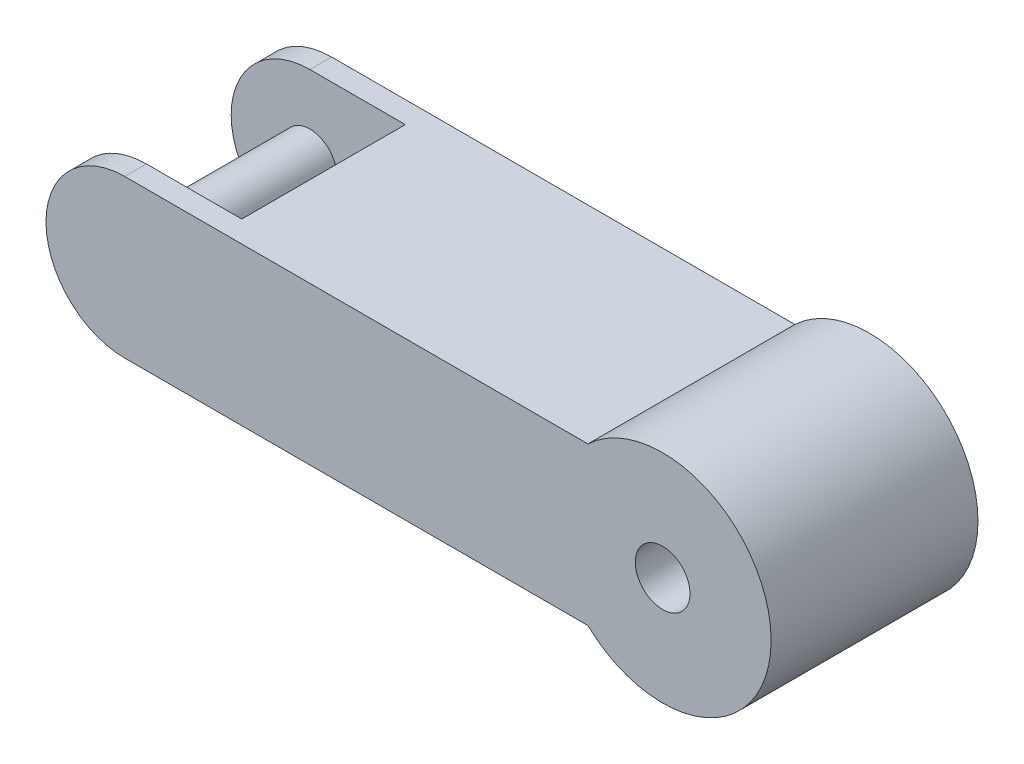
SolidWorks part; units mm, degrees
ref_plane "Front Plane" through (0, 0, 0) normal (0, 0, 1) x (1, 0, 0)
ref_plane "Top Plane" through (0, 0, 0) normal (0, 1, 0) x (1, 0, 0)
ref_plane "Right Plane" through (0, 0, 0) normal (1, 0, 0) x (0, 0, -1)
sketch "Sketch1" plane through (0, 0, 0) normal (0, 0, 1) x (1, 0, 0)
  line L1 (-13.7697, -14.5051) -> (-99.2033, -14.5051)
  line L3 (-13.7697, 14.5051) -> (-99.2033, 14.5051)
  line L5 (-94.0629, 13.5637) -> (-99.2033, 14.5051) construction
  line L6 (-94.0629, -13.5637) -> (-99.2033, -14.5051) construction
  circle A0 centre (0, 0) radius 20
  circle A1 centre (-99.2033, 0) radius 14.5051
  point P3 (-20, 0)
extrude "Boss-Extrude1" add sketch "Sketch1" along normal blind 4 contours A0 | A1 L1 A0 L3 | A1 region at (-52.9937, 0, 0) region at (0, 0, 0) region at (-99.2033, 0, 0)
sketch "Sketch2" plane through (0, 0, 4) normal (0, 0, 1) x (1, 0, 0)
  line L0 (-13.7697, 14.5051) -> (-99.2033, 14.5051) construction
  line L1 (-13.7697, -14.5051) -> (-99.2033, -14.5051) construction
  line L4 (-13.7697, 14.5051) -> (-99.2033, 14.5051)
  line L5 (-99.2033, -14.5051) -> (-13.7697, -14.5051)
  line L6 (-13.7697, 14.5051) -> (-83.4025, 14.5051)
  line L7 (-81.6041, -14.5051) -> (-13.7697, -14.5051)
  arc A0 (-83.4025, 14.5051) -> (-81.6041, -14.5051) centre (-82.5033, 0) cw
  arc A3 (-13.7697, -14.5051) -> (-13.7697, 14.5051) centre (0, 0) ccw
  arc A4 (-99.2033, 14.5051) -> (-99.2033, -14.5051) centre (-99.2033, 0) ccw
  arc A5 (-13.7697, -14.5051) -> (-13.7697, 14.5051) centre (0, 0) ccw
  arc M5 (-13.7697, -14.5051) -> (-13.7697, 14.5051) centre (0, 0) ccw
  line M6 (-13.7697, 14.5051) -> (-99.2033, 14.5051)
  line M8 (-99.2033, -14.5051) -> (-13.7697, -14.5051)
  dimension "D1" = 0
extrude "Boss-Extrude2" add sketch "Sketch2" along normal blind 15.075 contours A0 M6 M8 M5 region at (-24.5614, 0, 4)
mirror "Mirror1" about plane through (0, 0, 19.075) normal (0, 0, 1) of bodies 102
sketch "Sketch3" plane through (0, 0, 0) normal (0, 0, -1) x (-1, 0, 0)
  circle A0 centre (0, 0) radius 5.05
extrude "Cut-Extrude1" cut sketch "Sketch3" against normal blind 51.075
sketch "Sketch4" plane through (0, 0, 34.15) normal (0, 0, -1) x (-1, 0, 0)
  circle A1 centre (99.2033, 0) radius 5
extrude "Boss-Extrude3" add sketch "Sketch4" along normal blind 32.075 and the other way blind 2
